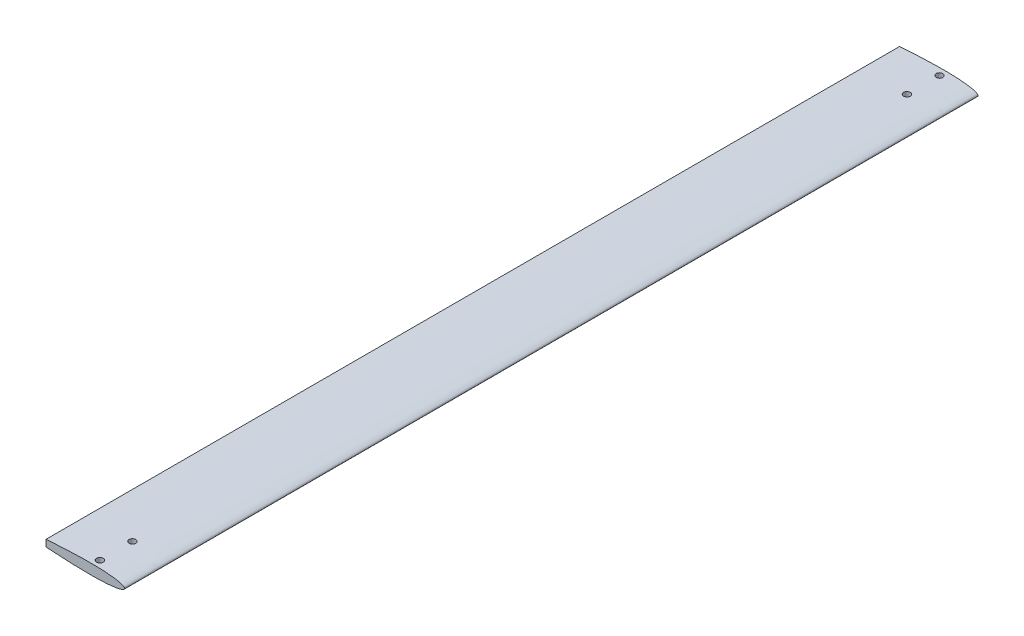
SolidWorks part; units mm, degrees
ref_plane "Front Plane" through (0, 0, 0) normal (0, 0, 1) x (1, 0, 0)
ref_plane "Top Plane" through (0, 0, 0) normal (0, 1, 0) x (1, 0, 0)
ref_plane "Right Plane" through (0, 0, 0) normal (1, 0, 0) x (0, 0, -1)
sketch "Sketch1" plane through (0, 0, 0) normal (0, 0, 1) x (1, 0, 0)
  line L0 (-84.3377, 3.5825) -> (-84.3377, -3.5825)
  spline S0 degree 3 poles (-84.3377, 3.5825) (-83.2839, 3.6579) (-80.141, 3.8826) (-74.8603, 4.2229) (-68.4728, 4.6006) (-62.0143, 4.9336) (-55.5558, 5.2118) (-49.1679, 5.4226) (-42.9205, 5.5549) (-36.8821, 5.5988) (-31.1187, 5.5465) (-25.6934, 5.3935) (-20.6656, 5.1381) (-16.0899, 4.7826) (-12.0164, 4.3324) (-8.4881, 3.7972) (-5.5434, 3.1852) (-3.2039, 2.5176) (-1.4947, 1.7846) (-0.3561, 1.0273) (0.1472, 0) (-0.3561, -1.0273) (-1.4947, -1.7846) (-3.2039, -2.5176) (-5.5434, -3.1852) (-8.4881, -3.7972) (-12.0164, -4.3324) (-16.0899, -4.7826) (-20.6656, -5.1381) (-25.6934, -5.3935) (-31.1187, -5.5465) (-36.8821, -5.5988) (-42.9205, -5.5549) (-49.1679, -5.4226) (-55.5558, -5.2118) (-62.0143, -4.9336) (-68.4728, -4.6006) (-74.8603, -4.2229) (-80.141, -3.8826) (-83.2839, -3.6579) (-84.3377, -3.5825) knots 0 0 0 0 0.018499 0.055171 0.092655 0.130539 0.168407 0.205846 0.242449 0.277819 0.311577 0.343364 0.372846 0.399719 0.423712 0.444594 0.46218 0.476354 0.487106 0.494669 0.5 0.505331 0.512894 0.523646 0.53782 0.555406 0.576288 0.600281 0.627154 0.656636 0.688423 0.722181 0.757551 0.794154 0.831593 0.869461 0.907345 0.944829 0.981501 1 1 1 1
extrude "Boss-Extrude1" add sketch "Sketch1" along normal mid plane 917.4
ref_plane "Plane1" through (0, -10, 0) normal (0, 1, 0) x (1, 0, 0)
sketch "Sketch2" plane through (0, -10, 0) normal (0, 1, 0) x (1, 0, 0)
  circle A0 centre (-33.9, -451.2) radius 3.6
  circle A1 centre (-33.9, -416.2) radius 3.6
  circle A2 centre (-33.9, 416.2) radius 3.6
  circle A3 centre (-33.9, 451.2) radius 3.6
extrude "Cut-Extrude1" cut sketch "Sketch2" along normal blind 20
